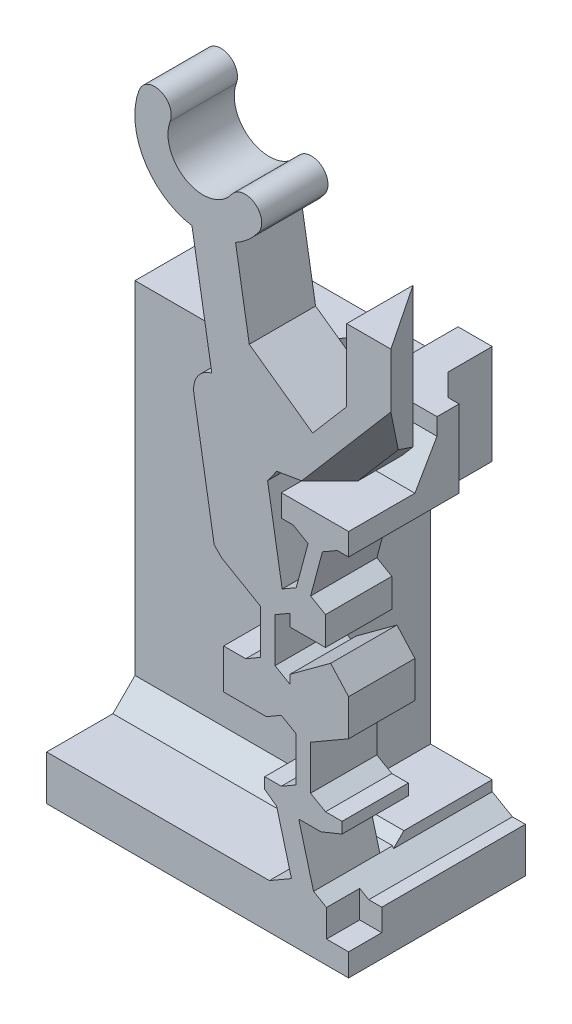
SolidWorks part; units mm, degrees
material "Nylon 6/12"
ref_plane "Front Plane" through (0, 0, 0) normal (0, 0, 1) x (1, 0, 0)
ref_plane "Top Plane" through (0, 0, 0) normal (0, 1, 0) x (1, 0, 0)
ref_plane "Right Plane" through (0, 0, 0) normal (1, 0, 0) x (0, 0, -1)
sketch "Sketch-SkeletonConfigUp" plane through (0, 0, 0) normal (0, 0, 1) x (1, 0, 0)
  line L0 (0, 0) -> (0, -50000) construction
  line L1 (0, 0) -> (4.5811, 6.2164) construction
  line L2 (9.8143, 13.3177) -> (4.5811, 13.945) construction
  line L3 (4.5811, 13.945) -> (2.9713, 10.4094) construction
  line L4 (2.9713, 10.4094) -> (4.5811, 6.2164) construction
  line L5 (4.5811, 13.945) -> (6.2429, 19.1409) construction
  line L6 (2.9713, 10.4094) -> (0.0405, 27.8193) construction
  line L7 (4.5811, 6.2164) -> (9.8143, 13.3177) construction
  line L8 (-587.3593, -797.0242) -> (9.8143, 13.3177) construction
  dimension "D2" = 7.7221
  dimension "D3" = 8.8212
  dimension "D4" = 5.2707
  dimension "D5" = 119.553
  dimension "D6" = 3.8848
  dimension "D7" = 5.4552
  dimension "D8" = 17.6549
  dimension "D9" = 4.4914
  dimension "D10" = 6.745
  dimension "D11" = 145.964
  dimension "D12" = 143.612
sketch "Sketch-SkeletonConfigDown" plane through (0, 0, 0) normal (0, 0, 1) x (1, 0, 0)
  line L0 (0, 0) -> (0, -50000) construction
  line L1 (0, 0) -> (4.5811, 6.2164) construction
  line L2 (9.8143, 13.3177) -> (4.5811, 13.945) construction
  line L3 (4.5811, 13.945) -> (6.1909, 10.4094) construction
  line L4 (6.1909, 10.4094) -> (4.5811, 6.2164) construction
  line L5 (4.5811, 13.945) -> (1.753, 18.6098) construction
  line L6 (6.1909, 10.4094) -> (-8.8652, 19.6294) construction
  line L7 (4.5811, 6.2164) -> (9.8143, 13.3177) construction
  line L8 (-589.9357, -800.5203) -> (9.8143, 13.3177) construction
  dimension "D2" = 7.7221
  dimension "D3" = 8.8212
  dimension "D4" = 5.2707
  dimension "D5" = 119.553
  dimension "D6" = 3.8848
  dimension "D7" = 5.4552
  dimension "D8" = 17.6549
  dimension "D9" = 4.4914
  dimension "D10" = 6.745
  dimension "D11" = 145.964
  dimension "D1" = 143.612
ref_plane "Plane-Cam Base" through (9.128, 0, 0) normal (1, 0, 0) x (0, 0, -1)
ref_plane "Plane-Down-to-Up Derailleur Clearance" through (6.628, 0, 0) normal (1, 0, 0) x (0, 0, -1)
ref_plane "Plane-Cam Cavity Roof" through (5.128, 0, 0) normal (1, 0, 0) x (0, 0, -1)
sketch "Sketch-SwitchBossUp" plane through (0, 0, 0) normal (0, 0, 1) x (1, 0, 0)
  line L0 (3.5811, 11.4759) -> (3.5811, 12.945) construction
  line L2 (6.5405, 21.1774) -> (6.5405, 24.4384)
  line L3 (6.5405, 24.4384) -> (8.5405, 24.4384)
  line L4 (8.5405, 24.4384) -> (8.5405, 20.4384)
  line L5 (5.5811, 12.5552) -> (5.5811, 11.263)
  line L7 (1.5115, 25.1048) -> (2.5464, 18.9575)
  line L8 (-0.4607, 24.7728) -> (0.4359, 19.4465)
  line L9 (2.9713, 10.4094) -> (0.0405, 27.8193) construction
  line L11 (-0.0396, 22.2712) -> (1.9326, 22.6032) construction
  line L15 (6.628, -55) -> (6.628, 55) construction
  line L16 (2.9713, 10.4094) -> (4.5811, 6.2164) construction
  line L17 (3.5811, 12.945) -> (3.5811, 14.945) construction
  line L18 (5.5811, 12.945) -> (5.5811, 14.945) construction
  line L19 (4.2561, 13.945) -> (4.9061, 13.945) construction
  line L20 (3.5811, 14.945) -> (5.5811, 14.945) construction
  line L21 (3.5811, 12.945) -> (5.5811, 12.945) construction
  line L22 (4.5811, 12.945) -> (4.5811, 14.945) construction
  line L23 (4.5811, 6.2164) -> (8.5405, 7.1023) construction
  line L24 (1.9713, 9.4094) -> (1.9713, 11.4094) construction
  line L25 (3.9713, 9.4094) -> (3.9713, 11.4094) construction
  line L26 (3.9713, 9.4094) -> (1.9713, 9.4094) construction
  line L27 (1.9713, 11.4094) -> (3.9713, 11.4094) construction
  line L28 (3.5811, 7.2164) -> (5.5811, 7.2164) construction
  line L29 (3.5811, 7.2164) -> (3.5811, 5.2164) construction
  line L30 (5.5811, 7.2164) -> (5.5811, 5.2164) construction
  line L31 (3.5811, 5.2164) -> (5.5811, 5.2164) construction
  line L32 (4.9061, 6.2164) -> (4.2561, 6.2164) construction
  line L40 (3.2963, 10.4094) -> (2.6463, 10.4094) construction
  line L43 (2.874, 4.5093) -> (0.7934, 4.5093) construction
  line L51 (4.9929, 19.3693) -> (2.5464, 18.9575)
  line L66 (0.0405, 27.8193) -> (0.0405, 50027.8193) construction
  line L74 (0.5455, 12.7717) -> (-0.3728, 18.2264)
  line L75 (0.3841, 13.7302) -> (2.3564, 14.0622) construction
  line L76 (5.5811, 11.263) -> (5.5811, 12.5552) construction
  line L77 (5.5811, 7.6061) -> (6.628, 8.2105)
  line L80 (5.8152, 10.763) -> (6.628, 9.8603)
  line L81 (8.5405, 1033.6218) -> (8.5405, 20.4384) construction
  line L82 (2.5464, 18.9575) -> (3.5585, 12.945) construction
  line L83 (3.6203, 12.5779) -> (2.8784, 16.9852)
  line L84 (2.8784, 16.9852) -> (6.0405, 17.5175)
  line L85 (6.9307, 9.5241) -> (8.5405, 7.7363) construction
  line L88 (3.5811, 16.3347) -> (6.8573, 16.3347)
  line L92 (3.7762, 8.3129) -> (6.9307, 9.5241) construction
  line L93 (6.3311, 4.3267) -> (5.3706, 3.937)
  line L95 (2.5464, 18.9575) -> (2.8784, 16.9852) construction
  line L96 (2.7124, 17.9713) -> (8.5405, 18.9524) construction
  line L97 (2.7124, 17.9713) -> (1.7262, 17.8053) construction
  line L98 (1.9713, 9.0197) -> (0.9713, 9.0197)
  line L99 (0.9713, 9.0197) -> (0.9713, 7.2164)
  line L100 (0.9713, 7.2164) -> (2.9061, 7.2164)
  line L101 (4.5811, 6.2164) -> (6.9307, 9.5241) construction
  line L103 (0.0405, 27.8193) -> (1.9448, 26.4638) construction
  line L104 (6.9307, 9.5241) -> (8.5405, 7.7363) construction
  line L106 (13.4416, 14.945) -> (5.5811, 14.945) construction
  line L107 (1.9713, 9.4094) -> (1.9713, 9.0197) construction
  line L109 (0.0405, 27.8193) -> (-2.1498, 28.6358) construction
  line L110 (8.5405, 20.4384) -> (6.0405, 17.5175)
  line L111 (6.628, 9.8603) -> (6.628, 8.2105)
  line L112 (6.628, 9.8603) -> (6.9307, 9.5241) construction
  line L113 (2.8311, 4.8267) -> (2.8311, 4.3267)
  line L114 (7.3693, 7.7363) -> (7.3563, 7.7363) construction
  line L115 (6.8573, 16.3347) -> (13.4416, 16.3347)
  line L116 (13.4416, 16.3347) -> (13.4416, -1.1653)
  line L117 (13.4416, -1.1653) -> (5.0405, -1.1653)
  line L119 (10.4375, 14.0252) -> (10.4375, 2.1692)
  line L121 (5.0405, -1.1653) -> (5.0405, 1.437) construction
  line L122 (8.237, 12.8031) -> (10.8393, 12.8031) construction
  line L123 (10.8393, 12.8031) -> (13.4416, 12.8031) construction
  line L124 (10.4375, 2.1692) -> (9.128, 0.8597)
  line L125 (8.5405, 7.5847) -> (13.4416, 7.5847) construction
  line L127 (5.5811, 15.3347) -> (5.5811, 14.945) construction
  line L130 (6.0405, 0.8597) -> (9.128, 0.8597)
  line L132 (2.8311, 4.3267) -> (3.3706, 3.937)
  line L133 (2.9713, 10.4094) -> (6.1909, 10.4094) construction
  line L134 (4.5811, 10.4094) -> (4.5811, 13.945) construction
  line L135 (4.5811, 10.4094) -> (4.5811, 6.2164) construction
  line L136 (0.8973, 12.4192) -> (0.5455, 12.7717)
  line L137 (3.9713, 9.4094) -> (5.5811, 7.2164) construction
  line L139 (5.8152, 10.763) -> (3.9713, 9.4094)
  line L141 (4.0405, 1.437) -> (3.0405, 0.8597)
  line L142 (3.0405, 0.8597) -> (3.0405, -1.1653)
  line L143 (8.5405, 20.4384) -> (8.5405, 18.9524) construction
  line L145 (8.5405, 17.9384) -> (8.5405, -49992.0368) construction
  line L147 (5.5811, 11.263) -> (5.5811, 12.5552) construction
  line L149 (6.3311, 4.8267) -> (6.3311, 4.3267)
  line L150 (3.0405, -1.1653) -> (5.0405, -1.1653)
  line L151 (3.3706, 3.937) -> (5.3706, 3.937) construction
  line L152 (4.792, 14.945) -> (4.2561, 12.945)
  line L153 (5.442, 14.945) -> (4.9061, 12.945)
  line L157 (3.5811, 16.3347) -> (3.5811, 15.3347)
  line L158 (6.117, 15.3347) -> (9.128, 15.3347)
  line L162 (3.2963, 11.4094) -> (3.2963, 9.4094)
  line L164 (2.6463, 11.4094) -> (2.6463, 9.4094)
  line L169 (4.2561, 7.2164) -> (4.2561, 5.2164)
  line L170 (4.9061, 5.2164) -> (4.9061, 7.2164)
  line L175 (4.2561, 7.2164) -> (3.5811, 7.6061)
  line L176 (4.9061, 7.2164) -> (5.5811, 7.6061)
  line L177 (5.5811, 7.2164) -> (5.5811, 7.6061) construction
  line L179 (4.2561, 5.2164) -> (3.5811, 4.8267)
  line L180 (3.5811, 5.2164) -> (3.5811, 4.8267) construction
  line L181 (3.5811, 4.8267) -> (2.8311, 4.8267)
  line L183 (4.9061, 5.2164) -> (5.5811, 4.8267)
  line L184 (5.5811, 5.2164) -> (5.5811, 4.8267) construction
  line L186 (9.128, -55) -> (9.128, 55) construction
  line L187 (2.6463, 9.4094) -> (1.9713, 9.0197)
  line L188 (3.2963, 9.4094) -> (3.9713, 9.0197)
  line L189 (3.2963, 11.4094) -> (3.9713, 11.7991)
  line L190 (2.6463, 11.4094) -> (0.8973, 12.4192)
  line L191 (3.9713, 11.4094) -> (3.9713, 11.7991) construction
  line L192 (3.9713, 11.7991) -> (3.9713, 11.263)
  line L193 (4.9061, 12.945) -> (5.5811, 12.5552)
  line L194 (4.2561, 12.945) -> (3.6203, 12.5779)
  line L195 (3.9713, 11.263) -> (5.5811, 11.263)
  line L196 (3.9713, 9.4094) -> (3.9713, 9.0197)
  line L197 (3.5811, 7.2164) -> (3.5811, 7.6061) construction
  line L199 (3.5811, 7.6061) -> (2.9061, 7.2164)
  line L200 (5.5811, 4.8267) -> (6.3311, 4.8267)
  line L201 (2.8311, 4.3267) -> (2.8311, 3.937) construction
  line L202 (2.8311, 3.937) -> (3.3706, 3.937) construction
  line L203 (10.4375, 14.0252) -> (9.128, 15.3347)
  line L204 (5.0405, 1.437) -> (3.0405, 1.437) construction
  line L205 (3.0405, 1.437) -> (3.0405, 0.8597) construction
  line L206 (5.0405, 1.437) -> (6.0405, 0.8597)
  line L207 (8.5405, 18.9524) -> (8.5405, 17.9384) construction
  line L208 (6.0405, 17.5175) -> (8.5405, 17.9384) construction
  line L209 (8.5405, 20.4384) -> (8.5405, 17.9384) construction
  line L210 (6.5405, 21.1774) -> (4.9929, 19.3693)
  line L211 (5.0405, 1.437) -> (4.3706, 3.937)
  line L212 (4.0405, 1.437) -> (3.3706, 3.937)
  line L213 (5.3706, 3.937) -> (4.3706, 3.937)
  line L214 (4.792, 14.945) -> (4.1169, 15.3347)
  line L215 (4.1169, 15.3347) -> (3.5811, 15.3347)
  line L216 (5.442, 14.945) -> (6.117, 15.3347)
  line L217 (5.5811, 12.945) -> (5.5811, 12.5552) construction
  line L218 (5.442, 14.945) -> (5.442, 15.3347) construction
  line L219 (6.117, 15.3347) -> (4.1169, 15.3347) construction
  arc A0 (1.5115, 25.1048) -> (2.5558, 26.0289) centre (0.0405, 27.8193) ccw
  arc A1 (-0.4607, 24.7728) -> (-2.8525, 28.8978) centre (0.0405, 27.8193) cw
  arc A2 (-2.8525, 28.8978) -> (-1.447, 28.3738) centre (-2.1498, 28.6358) cw
  arc A3 (2.5558, 26.0289) -> (1.3338, 26.8987) centre (1.9448, 26.4638) ccw
  arc A4 (-1.447, 28.3738) -> (1.3338, 26.8987) centre (0.0405, 27.8193) ccw
  arc A5 (3.5811, 12.945) -> (3.5811, 14.945) centre (3.1778, 13.945) ccw construction
  arc A6 (5.5811, 12.945) -> (5.5811, 14.945) centre (5.9843, 13.945) cw construction
  arc A7 (2.5293, 9.921) -> (1.9713, 11.4094) centre (1.568, 10.4094) ccw construction
  arc A8 (3.9713, 11.4094) -> (3.9713, 9.4094) centre (4.3745, 10.4094) ccw construction
  arc A9 (3.5811, 7.2164) -> (3.5811, 5.2164) centre (3.1779, 6.2164) cw construction
  arc A10 (5.5811, 7.2164) -> (5.5811, 5.2164) centre (5.9844, 6.2164) ccw construction
  arc A19 (-0.3728, 18.2264) -> (0.4359, 19.4465) centre (0.6836, 18.4042) cw
  circle A28 centre (0.0405, 27.8193) radius 2.3375 construction
  arc A29 (1.9713, 9.4094) -> (2.5293, 9.921) centre (1.568, 10.4094) ccw construction
  point P53 (4.5811, 13.945)
  point P63 (2.9713, 10.4094)
  point P93 (0.9465, 22.4372)
  dimension "D23" = 1.5875
  dimension "D24" = 0.75
  dimension "D2" = 2
  dimension "D5" = 2
  dimension "D6" = 0.65
  dimension "D8" = 42
  dimension "D7" = 2
  dimension "D11" = 8.5
  dimension "D14" = 7.5
  dimension "D4" = 3
  dimension "D16" = 42
  dimension "D27" = 120
  dimension "D28" = 120
  dimension "D29" = 120
  dimension "D30" = 120
  dimension "D31" = 120
  dimension "D32" = 120
  dimension "D33" = 120
  dimension "D34" = 120
  dimension "D17" = 0.5
  dimension "D20" = 3.5
  dimension "D21" = 1
  dimension "D18" = 45
  dimension "D9" = 17.5
  dimension "D22" = 1
  dimension "D15" = 45
  dimension "D38" = 2
  dimension "D39" = 0.5
  dimension "D40" = 60
  dimension "D41" = 1
  dimension "D42" = 45
  dimension "D43" = 120
  dimension "D44" = 2
  dimension "D45" = 2.5
  dimension "D46" = 2.5
  dimension "D47" = 4
  dimension "D48" = 2
  dimension "D10" = 15
  dimension "D12" = 2.5
  dimension "D13" = 1
  dimension "D19" = 1
  dimension "D25" = 15
  dimension "D26" = 120
  dimension "D35" = 120
extrude "Boss-Switch Body" add sketch "Sketch-SwitchBossUp" along normal blind 3
sketch "Sketch1" plane through (0, 0, 0) normal (0, 0, -1) x (-1, 0, 0)
  line L1 (-7.5811, -1.1653) -> (0.4122, -1.1653)
  line L2 (-7.5811, -1.1653) -> (-7.5811, 0.8597)
  line L4 (0.4122, -1.1653) -> (0.4122, 0.8597)
  line L5 (-3.5811, 18.8347) -> (-7.5811, 18.8347)
  line L10 (-7.5811, 18.8347) -> (-7.5811, 15.3347)
  line L11 (-4.0405, 1.437) -> (-5.0405, 1.437)
  line L12 (-7.5811, 15.3347) -> (-3.5811, 15.3347)
  line L13 (-4.0405, 1.437) -> (-3.0405, 0.8597)
  line L14 (-3.5811, 15.3347) -> (-3.5811, 18.8347)
  line L20 (-4.3706, 3.937) -> (-5.0405, 1.437) construction
  line L22 (-3.0405, -1.1653) -> (-13.4416, -1.1653) construction
  line L23 (-3.0405, 0.8597) -> (0.4122, 0.8597)
  line L24 (-5.0405, 1.437) -> (-6.0405, 0.8597)
  line L25 (-6.0405, 0.8597) -> (-7.5811, 0.8597)
  line L27 (-3.5811, 16.3347) -> (-3.5811, 15.3347) construction
  dimension "D1" = 3.5
  dimension "D4" = 4
extrude "Boss-Flange Width" add sketch "Sketch1" along normal blind 5
ref_plane "Plane-Sta2Sit Groove" through (0.0405, 0, 0) normal (1, 0, 0) x (0, 0, -1)
ref_plane "Plane-Cam Outer Surface" through (-12.0395, 0, 0) normal (1, 0, 0) x (0, 0, -1)
ref_plane "Plane-FlangeTop" through (-7.0395, 0, 0) normal (1, 0, 0) x (0, 0, -1)
sketch "Sketch2" plane through (-7.0395, 0, 0) normal (1, 0, 0) x (0, 0, -1)
  line L0 (5, 15.3347) -> (-3, 15.3347) construction
  line L1 (5, 17.3347) -> (1, 17.3347)
  line L2 (5, 17.3347) -> (5, 15.3347)
  line L3 (5, 15.3347) -> (1, 15.3347)
  line L4 (1, 17.3347) -> (1, 15.3347)
  line L10 (-3, -1.1653) -> (-3, 16.3347) construction
  line L11 (5, 0.8597) -> (-3, 0.8597)
  line L12 (5, 0.8597) -> (5, -1.1653)
  line L13 (5, -1.1653) -> (-3, -1.1653)
  line L14 (-3, 0.8597) -> (-3, -1.1653)
  line L15 (0, 10.4094) -> (0, 27.8193) construction
  line L17 (5, 0.8597) -> (5, -1.1653) construction
  line L18 (-3, 0.8597) -> (0, 0.8597) construction
  dimension "D1" = 1
  dimension "D2" = 2
extrude "Boss-Flange Height" add sketch "Sketch2" along normal up to surface (11.6675 mm away)
sketch "Sketch10" plane through (0, 15.3347, 0) normal (0, 1, 0) x (1, 0, 0)
  line L0 (9.128, -55) -> (9.128, 55) construction
  line L1 (7.5811, 5) -> (5.128, 5)
  line L2 (7.5811, 5) -> (7.5811, 2)
  line L3 (7.5811, 2) -> (5.128, 2)
  line L5 (4.628, 7) -> (4.628, 1) construction
  line L6 (3.5811, 1) -> (-7.0395, 1) construction
  line L8 (5.128, 5) -> (5.128, 2)
  dimension "D1" = 1
  dimension "D2" = 0.5
  dimension "D3" = 4.5
extrude "Cut-Up-To-Down Derailleur Clearance" cut sketch "Sketch10" along normal up to next
sketch "Sketch17" plane through (0, 15.3347, 0) normal (0, -1, 0) x (1, 0, 0)
  line L0 (5.128, -5) -> (-7.0395, -5)
  line L1 (5.128, -5) -> (-7.0395, -5) construction
  line L2 (-7.0395, -5) -> (-7.0395, -1)
  line L3 (-7.0395, -1) -> (5.128, -1)
  line L4 (5.128, -1) -> (5.128, -5)
  line L5 (-7.0395, -1) -> (-7.0395, -5) construction
extrude "Boss-Flange Support" add sketch "Sketch17" along normal up to surface (14.475 mm away) up to face at (-1.9995, 0.8597, -1)
sketch "Sketch-HolePositions" plane through (0, -1.1653, 0) normal (0, -1, 0) x (1, 0, 0)
  line L0 (-7.0395, -3) -> (7.5811, -3) construction
  line L1 (7.5811, -5) -> (-7.0395, -5) construction
  line L2 (7.5811, -5) -> (7.5811, 0) construction
  line L4 (-7.0395, -22.2167) -> (-7.0395, 22.2167) construction
  line L5 (3.5811, -1) -> (3.5811, -5) construction
  point P6 (-4.0395, -3)
  point P7 (0.5811, -3)
  dimension "D1" = 3
  dimension "D2" = 3
  dimension "D3" = 2
sketch "Sketch6" plane through (0, -1.1653, 0) normal (0, -1, 0) x (-1, 0, 0)
  point P0 (4.0395, 3)
  point P3 (-0.5811, 3)
hole_wizard "Tap Drill for M2x0.4 Tap1" positions "Sketch6" profile "Sketch5" hole size "M2x0.4" standard "ANSI Metric" end condition through all
sketch "Sketch5" plane through (-4.0395, -1.1653, -3) normal (1, 0, 0) x (0, 0, -1)
  line L0 (0, 0) -> (0, 30.5511)
  line L1 (0, 30.5511) -> (0.8, 30.5511)
  line L2 (0.8, 30.5511) -> (0.8, 0)
  line L5 (0.8, 0) -> (0, 0)
  line L11 (0, -6.35) -> (0, 107.95) construction
  dimension "Thru Hole Dia." = 1.6
  dimension "Thru Hole Depth" = 30.5511
sketch "Sketch9" plane through (0, -1.1653, 0) normal (0, -1, 0) x (1, 0, 0)
  point P0 (-4.0395, -3)
  point P3 (0.5811, -3)
hole_wizard "M2 Clearance Hole2" positions "Sketch9" profile "Sketch8" hole size "M2" standard "ANSI Metric"
sketch "Sketch8" plane through (-4.0395, -1.1653, -3) normal (1, 0, 0) x (0, 0, -1)
  line L0 (0, 0) -> (0, 15.721)
  line L1 (0, 15.721) -> (1.2, 15)
  line L2 (1.2, 15) -> (1.2, 0)
  line L5 (1.2, 0) -> (0, 0)
  line L10 (0, 15.721) -> (-1.2, 15) construction
  line L11 (0, -6.35) -> (0, 107.95) construction
  dimension "Hole Dia." = 2.4
  dimension "Hole Depth" = 15
  dimension "Drill Angle" = 118
sketch "Sketch-Measurements for Derailleur Ramps" plane through (0, 0, 0) normal (0, 0, 1) x (1, 0, 0)
  line L0 (2.8784, 16.9852) -> (2.5464, 18.9575)
  line L1 (2.7124, 17.9713) -> (1.7262, 17.8053)
  line L2 (2.9713, 10.4094) -> (0.0405, 27.8193) construction
  line L3 (1.7262, 17.8053) -> (-1.8937, 15.3603)
  line L4 (6.1909, 10.4094) -> (-8.8652, 19.6294) construction
  line L5 (1.7262, 17.8053) -> (2.6012, 12.6077)
  line L6 (2.6012, 12.6077) -> (-1.8937, 15.3603)
  line L7 (-0.0837, 16.5828) -> (-0.0837, 17.8053)
  line L8 (-0.0837, 17.8053) -> (1.7262, 17.8053)
  line L9 (6.1909, 10.4094) -> (2.9713, 10.4094)
  line L10 (5.386, 8.3129) -> (3.7762, 8.3129)
  line L12 (6.1909, 10.4094) -> (4.5811, 6.2164) construction
  line L13 (4.5811, 8.3129) -> (4.5811, 8.7912)
  line L14 (4.5811, 6.2164) -> (5.386, 8.3129)
  line L15 (2.9713, 10.4094) -> (4.5811, 6.2164) construction
  line L16 (3.7762, 8.3129) -> (4.5811, 6.2164)
  line L17 (5.386, 8.3129) -> (5.386, 8.7912)
  dimension "D1" = 1.81
  dimension "D2" = 0.8049
sketch "Sketch12" plane through (0, 24.4384, 0) normal (0, 1, 0) x (1, 0, 0)
  line L0 (6.5405, 0) -> (8.5405, -3)
  line L1 (8.5405, -3) -> (8.5405, 0)
  line L2 (8.5405, 0) -> (6.5405, 0)
extrude "Cut-Up-to-Down Cantilever Slope" cut sketch "Sketch12" against normal up to next
ref_plane "Plane1" through (0, 7.1023, 0) normal (0, 1, 0) x (1, 0, 0)
sketch "Sketch-Derailleur Location" plane through (0, 7.1023, 0) normal (0, 1, 0) x (1, 0, 0)
  line L0 (8.5405, 0) -> (8.5405, -3)
  line L1 (4.0405, -3) -> (3.0405, -3) construction
  line L2 (-119237.4187, 0) -> (9.8143, 0) construction
  point P0 (8.5405, 0)
  point P8 (8.5405, -1.5)
ref_plane "Plane-Cantilever Cut" [suppressed] through (7.0848, 8.5204, -1.9058) normal (-0.6301, -0.7578, 0.1695) x (-0.7765, 0.6151, -0.1368)
sketch "Sketch14" [suppressed] plane through (7.0848, 8.5204, -1.9058) normal (-0.6301, -0.7578, 0.1695) x (-0.7765, 0.6151, -0.1368)
  line L0 (2.3023, -1.6911) -> (-0.3551, -1.6911)
  line L2 (2.3023, -4.3362) -> (2.3023, -1.6911)
  line L3 (-0.3551, -1.6911) -> (-0.3551, -4.4608)
  line L5 (-0.3551, -4.4608) -> (1.0087, -5.0843)
  line L6 (1.0087, -5.0843) -> (2.3023, -4.3362)
extrude "Cut-Down-to-Up Cantilever Slope" [suppressed] cut sketch "Sketch14" against normal up to next
sketch "Sketch16" plane through (0, 0, 0) normal (0, 0, -1) x (-1, 0, 0)
  line L0 (-7.5811, 18.8347) -> (-13.4416, 18.8347)
  line L1 (-13.4416, 18.8347) -> (-13.4416, -1.1653)
  line L2 (-13.4416, -1.1653) -> (-6.628, -1.1653)
  line L3 (-13.4416, -1.1653) -> (-5.0405, -1.1653) construction
  line L4 (-6.628, -1.1653) -> (-6.628, 5.2038)
  line L5 (-6.628, 5.2038) -> (-8.0037, 5.2038)
  line L6 (-8.0037, 5.2038) -> (-8.0037, 12.0484)
  line L7 (-8.0037, 12.0484) -> (-6.628, 12.0484)
  line L8 (-6.628, 12.0484) -> (-6.628, 17.9477)
  line L9 (-6.628, 55) -> (-6.628, -55) construction
  line L10 (-3.5811, 18.8347) -> (-6.5405, 18.8347) construction
  line L11 (-7.5811, 18.8347) -> (-6.628, 17.9477)
extrude "Cut-Down-to-Up Derailleur Clearance" cut sketch "Sketch16" against normal through all and the other way through all
ref_plane "Plane-Symmetry Plane" through (0, 0, 1.5) normal (0, 0, 1) x (1, 0, 0)
sketch "Sketch-Cable Center Point" plane through (0, 0, 1.5) normal (0, 0, 1) x (1, 0, 0)
  line L0 (0.0405, 27.8193) -> (0.1722, 27.0366)
  line L1 (2.9713, 10.4094) -> (0.0405, 27.8193) construction
  point P0 (0.0405, 27.8193)
  dimension "D1" = 0.7937
chamfer "Chamfer-Flange Support" distance 1.5 angle 45 1 edges at (3.5811, 17.3347, -3)
chamfer "Chamfer-Flange Support 2" distance 1 angle 45 2 edges at (5.128, 17.0847, -2) (5.128, 15.3347, -1.5)
chamfer "Chamfer-Flange Support 3" distance 1 angle 45 1 edges at (-1.9995, 0.8597, -1)
sketch "Sketch18" plane through (6.628, 0, 0) normal (1, 0, 0) x (0, 0, -1)
  line L1 (-3, -0.1403) -> (-1.5, -0.1403)
  line L2 (-3, -0.1403) -> (-3, 1.437)
  line L3 (-3, 1.437) -> (-1.5, 1.437)
  line L4 (-1.5, -0.1403) -> (-1.5, 1.437)
  line L5 (0.5774, 1.437) -> (0, 1.437) construction
  line L6 (-3, -1.1653) -> (-3, 0.8597) construction
  line L7 (-3, 0.8597) -> (5, 0.8597) construction
  dimension "D1" = 1.5
  dimension "D2" = 1
extrude "Cut-Down-to-Up Derailleur Clearance 2" cut sketch "Sketch18" against normal blind 1
sketch "Sketch19" plane through (0, 0, 0) normal (0, 0, 1) x (1, 0, 0)
  line L7 (3.5811, 18.8983) -> (6.628, 18.8983)
  line L8 (6.628, 18.8983) -> (6.628, 16.3347)
  line L9 (6.628, 16.3347) -> (3.5811, 16.3347)
  line L10 (3.5811, 16.3347) -> (3.5811, 18.8983)
  line L11 (6.628, 16.3347) -> (6.628, 17.9477) construction
extrude "Cut-Up-to-Down Cantilever Clearance" cut sketch "Sketch19" against normal up to surface (1 mm away) up to face at (1.4435, 12.7784, -1)
chamfer "Chamfer1" distance 1 angle 60 1 edges at (5.1045, 16.3347, -1) first distance on face at (5.1045, 16.3347, 1)
chamfer "Chamfer3" distance 0.75 angle 60 1 edges at (3.5811, 16.7007, -1) first distance on face at (3.5811, 16.2811, 0.8)
chamfer "Chamfer4" distance 0.5 angle 60 1 edges at (4.205, 15.3347, -1) first distance on face at (5.0385, 15.3347, 0.5227)
chamfer "Chamfer5" distance 0.5 angle 45 1 edges at (2.8784, 16.9852, 1.5)
chamfer "Chamfer6" distance 2.5 angle 45 1 edges at (2.5464, 18.9575, 1.5)
chamfer "Chamfer7" distance 1 angle 45 1 edges at (7.2905, 18.978, 3)
sketch "Sketch22" plane through (0, 0, 0) normal (0, 0, 1) x (1, 0, 0)
  line L0 (6.628, 17.9477) -> (7.5811, 18.8347) construction
  line L1 (6.628, 18.8347) -> (7.5811, 18.8347) construction
  line L2 (6.628, 17.9477) -> (6.628, 18.8347) construction
  line L3 (6.628, 17.9477) -> (7.5811, 18.8347)
  line L4 (6.628, 18.8347) -> (7.5811, 18.8347)
  line L5 (6.628, 17.9477) -> (6.628, 18.8347)
extrude "Cut-Extrude3" cut sketch "Sketch22" against normal up to next
chamfer "Chamfer8" [suppressed] distance 0.5 angle 45
sketch "Sketch23" plane through (0, 0, -1) normal (0, 0, 1) x (1, 0, 0)
  line L0 (5.128, 1.8597) -> (2.3369, 1.8597)
  line L1 (-7.0395, 1.8597) -> (5.128, 1.8597) construction
  line L2 (2.3369, 1.8597) -> (2.3369, 14.3347)
  line L3 (2.3369, 14.3347) -> (5.128, 14.3347)
  line L4 (5.128, 14.3347) -> (5.128, 1.8597)
extrude "Cut-Gap for Printing" cut sketch "Sketch23" against normal through all
equation "\"axle-diameter\"=2"
equation "\"switch-thickness\"=12"
equation "\"base-width\"=4.0"
equation "\"axle-bushing-radius\"=3"
equation "\"clearance\"= 0.25"
equation "\"arm-width\"=1.5"
equation "\"min-diameter\"=70"
equation "\"alpha\"=143.6120"
equation "\"gamma\"=119.5526"
equation "\"delta\"=145.9637"
equation "\"epsilon\"=6.7452"
equation "\"l_AB\"=8.8212"
equation "\"l_AC\"=4.4914"
equation "\"l_BD\"=5.2707"
equation "\"l_CD\"=3.8848"
equation "\"l_CE\"=17.6549"
equation "\"l_DF\"=5.4552"
equation "\"l_OA\"=7.7221"
equation "\"D2@Sketch-SkeletonConfigUp\" = \"l_OA\""
equation "\"D3@Sketch-SkeletonConfigUp\" = \"l_AB\""
equation "\"D4@Sketch-SkeletonConfigUp\" = \"l_BD\""
equation "\"D5@Sketch-SkeletonConfigUp\" = \"gamma\""
equation "\"D6@Sketch-SkeletonConfigUp\" = \"l_CD\""
equation "\"D7@Sketch-SkeletonConfigUp\" = \"l_DF\""
equation "\"D8@Sketch-SkeletonConfigUp\" = \"l_CE\""
equation "\"D9@Sketch-SkeletonConfigUp\" = \"l_AC\""
equation "\"D_groove\"=3.175"
equation "\"D7@Sketch-SkeletonConfigDown\" = \"l_DF\""
equation "\"D6@Sketch-SkeletonConfigDown\" = \"l_CD\""
equation "\"D2@Sketch-SkeletonConfigDown\" = \"l_OA\""
equation "\"D3@Sketch-SkeletonConfigDown\" = \"l_AB\""
equation "\"D9@Sketch-SkeletonConfigDown\" = \"l_AC\""
equation "\"D8@Sketch-SkeletonConfigDown\" = \"l_CE\""
equation "\"D5@Sketch-SkeletonConfigDown\" = \"gamma\""
equation "\"D4@Sketch-SkeletonConfigDown\" = \"l_BD\""
equation "\"D1@Sketch-SkeletonConfigDown\" = \"alpha\""
equation "\"hinge_length\"=1.5"
equation "\"hinge_depth\"=0.25"
equation "\"D10@Sketch-SkeletonConfigUp\"=\"epsilon\""
equation "\"D11@Sketch-SkeletonConfigUp\"=\"delta\""
equation "\"D12@Sketch-SkeletonConfigUp\"=\"alpha\""
equation "\"D11@Sketch-SkeletonConfigDown\"=\"delta\""
equation "\"D10@Sketch-SkeletonConfigDown\"=\"epsilon\""
equation "\"EE_dx\"=8.9056"
equation "\"EE_dy\"=8.1898"
equation "\"r_groove\"=\"D_groove\"/2"
equation "\"t_wall\"=25.4/16"
equation "\"width_lower\"=\"D_groove\"+\"t_wall\""
equation "\"cable_to_bottom\"=30.6257"
equation "\"switch_EE-up_base_dy\"=24"
equation "\"switch_EE-down_base_dy\"=16"
equation "\"D_axle\"=25.4/8"
equation "\"D_up_to_down\"=16"
equation "\"D_down_to_up\"=25"
equation "\"t_cam_base\"=7.5"
equation "\"D23@Sketch-SwitchBossUp\"=\"D_groove\"/2"
equation "\"D1@Sketch-Cable Center Point\"=\"D_groove\"/4"
